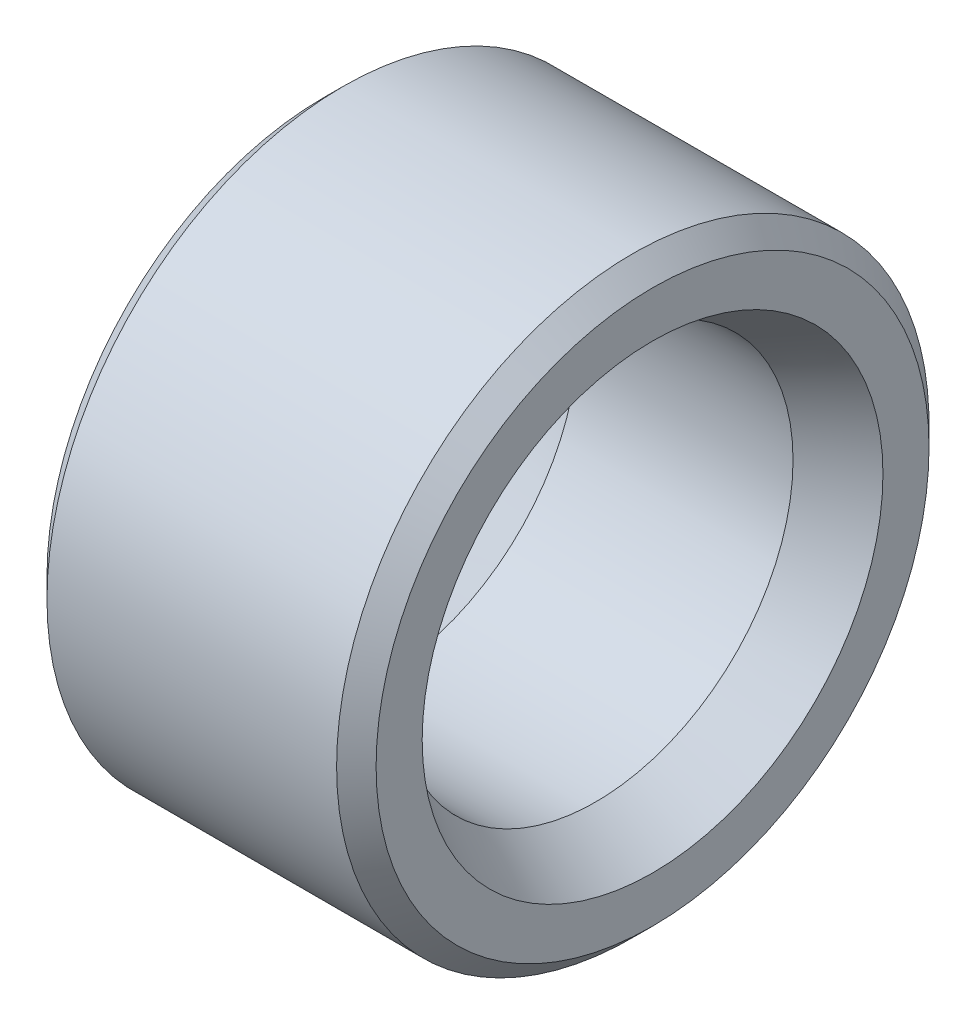
SolidWorks part; units mm, degrees
ref_plane "Front Plane" through (0, 0, 0) normal (0, 0, 1) x (1, 0, 0)
ref_plane "Top Plane" through (0, 0, 0) normal (0, 1, 0) x (1, 0, 0)
ref_plane "Right Plane" through (0, 0, 0) normal (1, 0, 0) x (0, 0, -1)
sketch "Sketch1" plane through (0, 0, 0) normal (0, 0, 1) x (1, 0, 0)
  line L0 (0, 0) -> (5, 0) construction
  line L1 (0, 3) -> (0, 4.5)
  line L2 (0, 4.5) -> (5, 4.5)
  line L4 (5, 4.5) -> (5, 3)
  line L6 (5, 3) -> (0, 3)
  dimension "L" = 5
  dimension "D_s" = 6
  dimension "D" = 9
  dimension "T" = 1.5
revolve "Revolve1" add sketch "Sketch1" angle 360 about L0
chamfer "Chamfer1" distance 0.3 angle 45 2 edges at (5, 0, 4.5) (0, 0, 4.5)
sketch "Sketch2" plane through (0, 0, 0) normal (0, 0, 1) x (1, 0, 0)
  line L0 (0, 0) -> (5, 0) construction
  line L1 (0, 3.5) -> (0, 3)
  line L2 (0, 3) -> (0.866, 3)
  line L3 (0.866, 3) -> (0, 3.5)
  line L4 (4.134, 3) -> (5, 3.5)
  line L5 (0, 3) -> (0, 4.5) construction
  line L8 (5, 3) -> (4.134, 3)
  line L9 (5, 3.5) -> (5, 3)
  line L10 (5, 3) -> (0, 3) construction
  line L11 (5, 4.5) -> (5, 3) construction
  dimension "FIX_4" = 0.5
  dimension "FIX_5" = 30
revolve "Cut-Revolve1" cut sketch "Sketch2" angle 360 about L0
